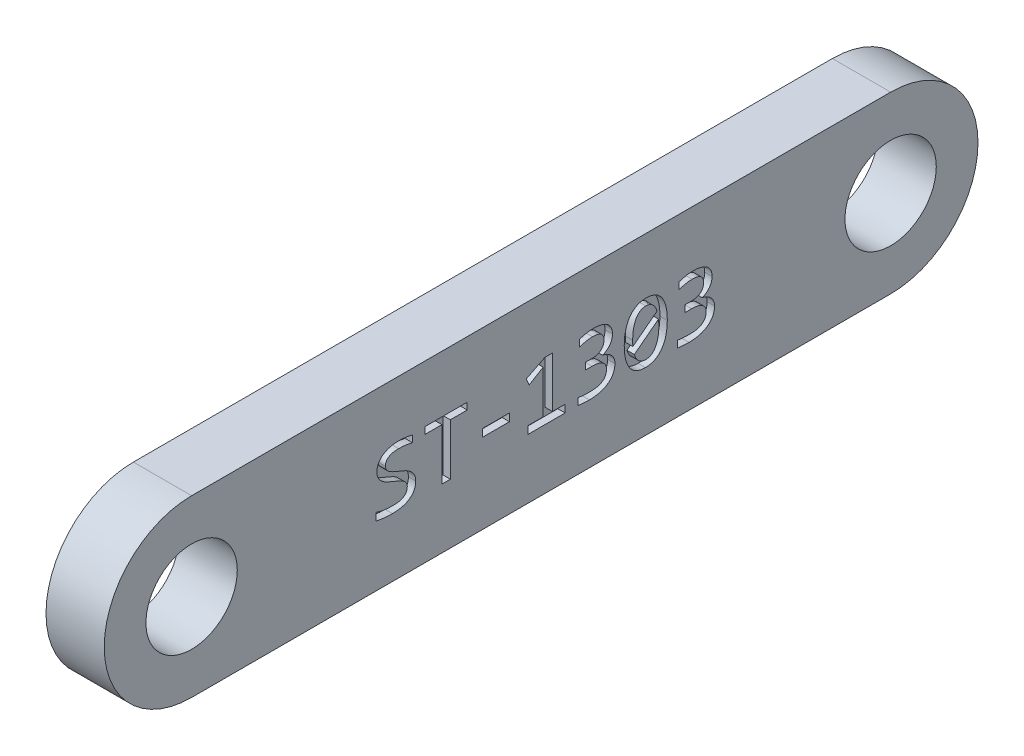
SolidWorks part; units mm, degrees
material "PET"
ref_plane "Front Plane" through (0, 0, 0) normal (0, 0, 1) x (1, 0, 0)
ref_plane "Top Plane" through (0, 0, 0) normal (0, 1, 0) x (1, 0, 0)
ref_plane "Right Plane" through (0, 0, 0) normal (1, 0, 0) x (0, 0, -1)
sketch "Sketch1" plane through (0, 0, 0) normal (1, 0, 0) x (0, 0, -1)
  line L0 (0, 0) -> (38.1, 0) construction
  line L1 (0, 4.7625) -> (38.1, 4.7625)
  line L2 (0, -4.7625) -> (38.1, -4.7625)
  arc A0 (0, 4.7625) -> (0, -4.7625) centre (0, 0) ccw
  arc A1 (38.1, -4.7625) -> (38.1, 4.7625) centre (38.1, 0) ccw
  circle A2 centre (38.1, 0) radius 2.4892
  circle A3 centre (0, 0) radius 2.4892
  point P3 (19.05, 0)
  dimension "D1" = 4.7625
  dimension "D3" = 4.9784
  dimension "D2" = 38.1
extrude "Boss-Extrude1" add sketch "Sketch1" along normal mid plane 3.175
sketch "Sketch2" plane through (0, 0, 0) normal (1, 0, 0) x (0, 0, -1)
  line L0 (-5.6204, -1.5106) -> (44.1758, -1.5106) construction
  text T0 "ST-1303" font "Consolas" height 3.175
extrude "Cut-Extrude1" cut sketch "Sketch2" against normal blind 0.4 from surface starting at face at (1.5875, 0, -40.5892)
